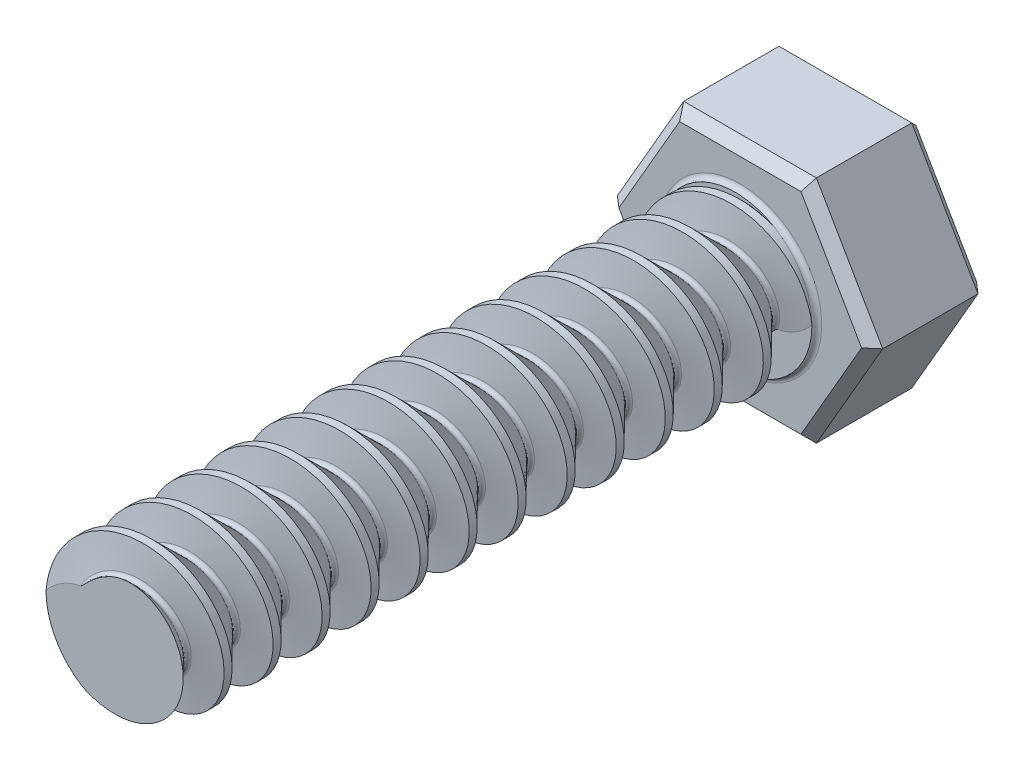
SolidWorks part; units mm, degrees
material "ABS"
ref_plane "Front Plane" through (0, 0, 0) normal (0, 0, 1) x (1, 0, 0)
ref_plane "Top Plane" through (0, 0, 0) normal (0, 1, 0) x (1, 0, 0)
ref_plane "Right Plane" through (0, 0, 0) normal (1, 0, 0) x (0, 0, -1)
sketch "Sketch1" plane through (0, 0, 0) normal (0, 0, 1) x (1, 0, 0)
  circle A0 centre (0, 0) radius 7.9375
  dimension "D1" = 15.875
extrude "Boss-Extrude1" add sketch "Sketch1" along normal blind 63.5
sketch "Sketch2" plane through (0, 0, 0) normal (0, 0, 1) x (1, 0, 0)
  circle A0 centre (0, 0) radius 7.9375
  circle A1 centre (0, 0) radius 7.9375 construction
curve "Helix/Spiral1" pitch 5.08 height 81.28 turns 16
sketch "Sketch3" plane through (0, 0, 0) normal (0, 1, 0) x (1, 0, 0)
  line L0 (7.9375, 0) -> (4.8895, -0.3742)
  line L1 (4.6772, -0.9907) -> (7.9375, -4.251)
  line L2 (7.9375, -63.5) -> (7.9375, 0) construction
  line L3 (8.6756, 0.4195) -> (8.6756, -3.3608) construction
  line L4 (7.9375, 0) -> (-7.9375, 0) construction
  line L5 (7.9375, -4.251) -> (7.9375, 0)
  arc A0 (4.6772, -0.9907) -> (4.8895, -0.3742) centre (4.9337, -0.7343) cw
  spline S0 degree 3 poles (7.9375, 0) (7.9375, -0.1052) (7.5242, -0.3178) (5.7588, -0.6349) (3.1166, -0.9525) (0, -1.27) (-3.1166, -1.5875) (-5.7588, -1.905) (-7.5242, -2.2225) (-8.1441, -2.54) (-7.5242, -2.8575) (-5.7588, -3.175) (-3.1166, -3.4925) (0, -3.81) (3.1166, -4.1275) (5.7588, -4.445) (7.5242, -4.7625) (8.1441, -5.08) (7.5242, -5.3975) (5.7588, -5.715) (3.1166, -6.0325) (0, -6.35) (-3.1166, -6.6675) (-5.7588, -6.985) (-7.5242, -7.3025) (-8.1441, -7.62) (-7.5242, -7.9375) (-5.7588, -8.255) (-3.1166, -8.5725) (0, -8.89) (3.1166, -9.2075) (5.7588, -9.525) (7.5242, -9.8425) (8.1441, -10.16) (7.5242, -10.4775) (5.7588, -10.795) (3.1166, -11.1125) (0, -11.43) (-3.1166, -11.7475) (-5.7588, -12.065) (-7.5242, -12.3825) (-8.1441, -12.7) (-7.5242, -13.0175) (-5.7588, -13.335) (-3.1166, -13.6525) (0, -13.97) (3.1166, -14.2875) (5.7588, -14.605) (7.5242, -14.9225) (8.1441, -15.24) (7.5242, -15.5575) (5.7588, -15.875) (3.1166, -16.1925) (0, -16.51) (-3.1166, -16.8275) (-5.7588, -17.145) (-7.5242, -17.4625) (-8.1441, -17.78) (-7.5242, -18.0975) (-5.7588, -18.415) (-3.1166, -18.7325) (0, -19.05) (3.1166, -19.3675) (5.7588, -19.685) (7.5242, -20.0025) (8.1441, -20.32) (7.5242, -20.6375) (5.7588, -20.955) (3.1166, -21.2725) (0, -21.59) (-3.1166, -21.9075) (-5.7588, -22.225) (-7.5242, -22.5425) (-8.1441, -22.86) (-7.5242, -23.1775) (-5.7588, -23.495) (-3.1166, -23.8125) (0, -24.13) (3.1166, -24.4475) (5.7588, -24.765) (7.5242, -25.0825) (8.1441, -25.4) (7.5242, -25.7175) (5.7588, -26.035) (3.1166, -26.3525) (0, -26.67) (-3.1166, -26.9875) (-5.7588, -27.305) (-7.5242, -27.6225) (-8.1441, -27.94) (-7.5242, -28.2575) (-5.7588, -28.575) (-3.1166, -28.8925) (0, -29.21) (3.1166, -29.5275) (5.7588, -29.845) (7.5242, -30.1625) (8.1441, -30.48) (7.5242, -30.7975) (5.7588, -31.115) (3.1166, -31.4325) (0, -31.75) (-3.1166, -32.0675) (-5.7588, -32.385) (-7.5242, -32.7025) (-8.1441, -33.02) (-7.5242, -33.3375) (-5.7588, -33.655) (-3.1166, -33.9725) (0, -34.29) (3.1166, -34.6075) (5.7588, -34.925) (7.5242, -35.2425) (8.1441, -35.56) (7.5242, -35.8775) (5.7588, -36.195) (3.1166, -36.5125) (0, -36.83) (-3.1166, -37.1475) (-5.7588, -37.465) (-7.5242, -37.7825) (-8.1441, -38.1) (-7.5242, -38.4175) (-5.7588, -38.735) (-3.1166, -39.0525) (0, -39.37) (3.1166, -39.6875) (5.7588, -40.005) (7.5242, -40.3225) (8.1441, -40.64) (7.5242, -40.9575) (5.7588, -41.275) (3.1166, -41.5925) (0, -41.91) (-3.1166, -42.2275) (-5.7588, -42.545) (-7.5242, -42.8625) (-8.1441, -43.18) (-7.5242, -43.4975) (-5.7588, -43.815) (-3.1166, -44.1325) (0, -44.45) (3.1166, -44.7675) (5.7588, -45.085) (7.5242, -45.4025) (8.1441, -45.72) (7.5242, -46.0375) (5.7588, -46.355) (3.1166, -46.6725) (0, -46.99) (-3.1166, -47.3075) (-5.7588, -47.625) (-7.5242, -47.9425) (-8.1441, -48.26) (-7.5242, -48.5775) (-5.7588, -48.895) (-3.1166, -49.2125) (0, -49.53) (3.1166, -49.8475) (5.7588, -50.165) (7.5242, -50.4825) (8.1441, -50.8) (7.5242, -51.1175) (5.7588, -51.435) (3.1166, -51.7525) (0, -52.07) (-3.1166, -52.3875) (-5.7588, -52.705) (-7.5242, -53.0225) (-8.1441, -53.34) (-7.5242, -53.6575) (-5.7588, -53.975) (-3.1166, -54.2925) (0, -54.61) (3.1166, -54.9275) (5.7588, -55.245) (7.5242, -55.5625) (8.1441, -55.88) (7.5242, -56.1975) (5.7588, -56.515) (3.1166, -56.8325) (0, -57.15) (-3.1166, -57.4675) (-5.7588, -57.785) (-7.5242, -58.1025) (-8.1441, -58.42) (-7.5242, -58.7375) (-5.7588, -59.055) (-3.1166, -59.3725) (0, -59.69) (3.1166, -60.0075) (5.7588, -60.325) (7.5242, -60.6425) (8.1441, -60.96) (7.5242, -61.2775) (5.7588, -61.595) (3.1166, -61.9125) (0, -62.23) (-3.1166, -62.5475) (-5.7588, -62.865) (-7.5242, -63.1825) (-8.1441, -63.5) (-7.5242, -63.8175) (-5.7588, -64.135) (-3.1166, -64.4525) (0, -64.77) (3.1166, -65.0875) (5.7588, -65.405) (7.5242, -65.7225) (8.1441, -66.04) (7.5242, -66.3575) (5.7588, -66.675) (3.1166, -66.9925) (0, -67.31) (-3.1166, -67.6275) (-5.7588, -67.945) (-7.5242, -68.2625) (-8.1441, -68.58) (-7.5242, -68.8975) (-5.7588, -69.215) (-3.1166, -69.5325) (0, -69.85) (3.1166, -70.1675) (5.7588, -70.485) (7.5242, -70.8025) (8.1441, -71.12) (7.5242, -71.4375) (5.7588, -71.755) (3.1166, -72.0725) (0, -72.39) (-3.1166, -72.7075) (-5.7588, -73.025) (-7.5242, -73.3425) (-8.1441, -73.66) (-7.5242, -73.9775) (-5.7588, -74.295) (-3.1166, -74.6125) (0, -74.93) (3.1166, -75.2475) (5.7588, -75.565) (7.5242, -75.8825) (8.1441, -76.2) (7.5242, -76.5175) (5.7588, -76.835) (3.1166, -77.1525) (0, -77.47) (-3.1166, -77.7875) (-5.7588, -78.105) (-7.5242, -78.4225) (-8.1441, -78.74) (-7.5242, -79.0575) (-5.7588, -79.375) (-3.1166, -79.6925) (0, -80.01) (3.1166, -80.3275) (5.7588, -80.6451) (7.5242, -80.9622) (7.9375, -81.1748) (7.9375, -81.28) knots 0 0 0 0 0.003906 0.007813 0.011719 0.015625 0.019531 0.023438 0.027344 0.03125 0.035156 0.039063 0.042969 0.046875 0.050781 0.054688 0.058594 0.0625 0.066406 0.070313 0.074219 0.078125 0.082031 0.085938 0.089844 0.09375 0.097656 0.101563 0.105469 0.109375 0.113281 0.117188 0.121094 0.125 0.128906 0.132813 0.136719 0.140625 0.144531 0.148438 0.152344 0.15625 0.160156 0.164063 0.167969 0.171875 0.175781 0.179688 0.183594 0.1875 0.191406 0.195313 0.199219 0.203125 0.207031 0.210938 0.214844 0.21875 0.222656 0.226563 0.230469 0.234375 0.238281 0.242188 0.246094 0.25 0.253906 0.257813 0.261719 0.265625 0.269531 0.273438 0.277344 0.28125 0.285156 0.289063 0.292969 0.296875 0.300781 0.304688 0.308594 0.3125 0.316406 0.320313 0.324219 0.328125 0.332031 0.335938 0.339844 0.34375 0.347656 0.351563 0.355469 0.359375 0.363281 0.367188 0.371094 0.375 0.378906 0.382813 0.386719 0.390625 0.394531 0.398438 0.402344 0.40625 0.410156 0.414063 0.417969 0.421875 0.425781 0.429688 0.433594 0.4375 0.441406 0.445313 0.449219 0.453125 0.457031 0.460938 0.464844 0.46875 0.472656 0.476563 0.480469 0.484375 0.488281 0.492188 0.496094 0.5 0.503906 0.507813 0.511719 0.515625 0.519531 0.523438 0.527344 0.53125 0.535156 0.539063 0.542969 0.546875 0.550781 0.554688 0.558594 0.5625 0.566406 0.570313 0.574219 0.578125 0.582031 0.585938 0.589844 0.59375 0.597656 0.601563 0.605469 0.609375 0.613281 0.617188 0.621094 0.625 0.628906 0.632813 0.636719 0.640625 0.644531 0.648438 0.652344 0.65625 0.660156 0.664063 0.667969 0.671875 0.675781 0.679688 0.683594 0.6875 0.691406 0.695313 0.699219 0.703125 0.707031 0.710938 0.714844 0.71875 0.722656 0.726563 0.730469 0.734375 0.738281 0.742188 0.746094 0.75 0.753906 0.757813 0.761719 0.765625 0.769531 0.773438 0.777344 0.78125 0.785156 0.789063 0.792969 0.796875 0.800781 0.804688 0.808594 0.8125 0.816406 0.820313 0.824219 0.828125 0.832031 0.835938 0.839844 0.84375 0.847656 0.851563 0.855469 0.859375 0.863281 0.867188 0.871094 0.875 0.878906 0.882813 0.886719 0.890625 0.894531 0.898438 0.902344 0.90625 0.910156 0.914063 0.917969 0.921875 0.925781 0.929688 0.933594 0.9375 0.941406 0.945313 0.949219 0.953125 0.957031 0.960938 0.964844 0.96875 0.972656 0.976563 0.980469 0.984375 0.988281 0.992188 0.996094 1 1 1 1 construction
  point P13 (4.1514, -0.4649)
  dimension "D5" = 0.3627
  dimension "D1" = 0.7381
  dimension "D2" = 4.5242
  dimension "D3" = 7
  dimension "D4" = 45
sweep "Cut-Sweep1" cut profiles "Sketch3" path "Helix/Spiral1"
sketch "Sketch5" plane through (0, 0, 0) normal (0, 0, -1) x (-1, 0, 0)
  circle A0 centre (0, 0) radius 7.9375
  circle A1 centre (0, 0) radius 7.9375 construction
extrude "Boss-Extrude3" add sketch "Sketch5" along normal blind 0.508
sketch "Sketch6" plane through (0, 0, -0.508) normal (0, 0, -1) x (-1, 0, 0)
  line L1 (13.7482, 0) -> (6.8741, 11.9063)
  line L2 (6.8741, 11.9063) -> (-6.8741, 11.9063)
  line L3 (-6.8741, 11.9063) -> (-13.7482, 0)
  line L4 (-13.7482, 0) -> (-6.8741, -11.9062)
  line L5 (-6.8741, -11.9062) -> (6.8741, -11.9062)
  line L6 (6.8741, -11.9062) -> (13.7482, 0)
  circle A0 centre (0, 0) radius 11.9062 construction
  dimension "D1" = 23.8125
extrude "Boss-Extrude4" add sketch "Sketch6" along normal blind 11.9062
fillet "Fillet1" radius 0.508 1 edges at (-7.9375, 0, -0.508)
chamfer "Chamfer1" distance 1.016 angle 45 12 edges at (10.3111, -5.9531, -12.4142) (10.3111, 5.9531, -12.4142) (0, 11.9063, -12.4142) (-10.3111, 5.9531, -12.4142) (-10.3111, -5.9531, -12.4142) (0, -11.9062, -12.4142) (0, 11.9063, -0.508) (10.3111, 5.9531, -0.508) (10.3111, -5.9531, -0.508) (0, -11.9062, -0.508) (-10.3111, -5.9531, -0.508) (-10.3111, 5.9531, -0.508)
equation "\"Pitch\"= 1 / 5"
equation "\"D1@Sketch3\"=\"Pitch\"*.1453"
equation "\"D2@Sketch3\"=\"Pitch\"*.8906"
equation "\"D5@Sketch3\"=\"Pitch\"*.0714"
